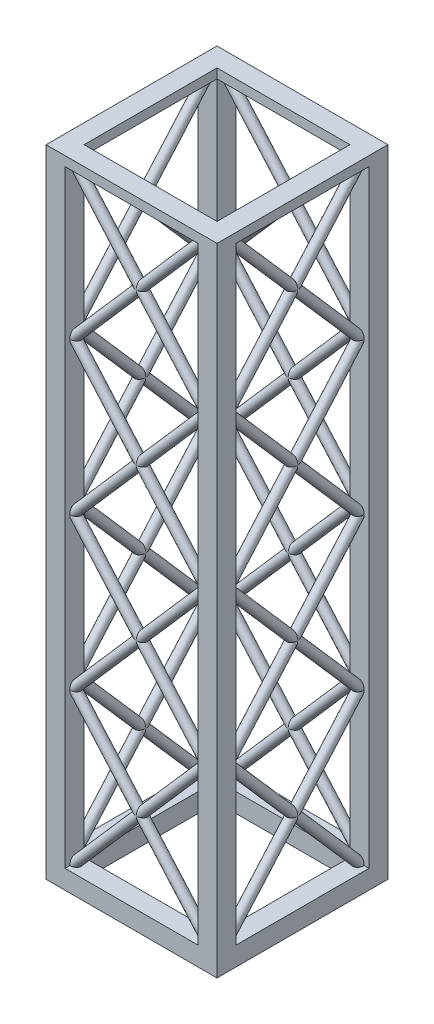
SolidWorks part; units mm, degrees
note: '?' marks a value the reader was unsure of.
ref_plane "Front Plane" through (0, 0, 0) normal (0, 0, 1) x (1, 0, 0)
ref_plane "Top Plane" through (0, 0, 0) normal (0, 1, 0) x (1, 0, 0)
ref_plane "Right Plane" through (0, 0, 0) normal (1, 0, 0) x (0, 0, -1)
sketch "Sketch1" plane through (0, 0, 0) normal (0, 1, 0) x (1, 0, 0)
  line L0 (-45, 45) -> (-45, -45)
  line L1 (-40, 40) -> (40, 40) construction
  line L2 (-40, 40) -> (-40, -40) construction
  line L3 (-40, -40) -> (40, -40) construction
  line L4 (40, 40) -> (40, -40) construction
  line L5 (-40, 40) -> (40, -40) construction
  line L6 (-40, -40) -> (40, 40) construction
  line L11 (-45, -45) -> (45, -45)
  line L12 (45, 45) -> (45, -45)
  line L13 (-45, 45) -> (45, 45)
  line L14 (-35, 35) -> (-35, -35)
  line L15 (-35, -35) -> (35, -35)
  line L16 (35, 35) -> (35, -35)
  line L17 (-35, 35) -> (35, 35)
  point P0 (0, 0)
  dimension "D1" = 80
  dimension "D2" = 80
  dimension "D3" = 5
  dimension "D4" = 5
ref_axis "Axis1" through (0, 367.5, 0) along (0, -1, 0)?
extrude "Boss-Extrude2" add sketch "Sketch1" along normal blind 10
sketch "Sketch2" plane through (0, 10, 0) normal (0, 1, 0) x (1, 0, 0)
  line L0 (-35, -35) -> (-45, -45) construction
  line L2 (-45, -45) -> (-35, -45)
  line L3 (-45, -45) -> (-45, -35)
  line L4 (-45, -35) -> (-35, -35)
  line L5 (-35, -45) -> (-35, -35)
  line L6 (-45, -45) -> (-35, -35) construction
  line L7 (-45, -35) -> (-35, -45) construction
  point P4 (-40, -40)
extrude "Boss-Extrude3" add sketch "Sketch2" along normal blind 320
pattern_circular "CirPattern2" count 4 over 360 about axis through (0, 0, 0) along (0, 1, 0) of "Boss-Extrude3"
sketch "Sketch3" plane through (0, 330, 0) normal (0, 1, 0) x (1, 0, 0)
  line L0 (-35, -35) -> (35, -35) construction
  line L1 (-45, -45) -> (45, -45)
  line L2 (-45, -45) -> (-45, 45)
  line L3 (-45, 45) -> (45, 45)
  line L4 (45, -45) -> (45, 45)
  line L5 (-45, -45) -> (45, 45) construction
  line L6 (-45, 45) -> (45, -45) construction
  line L7 (35, -35) -> (35, 35) construction
  line L8 (35, 35) -> (-35, 35) construction
  line L9 (-35, 35) -> (-35, -35) construction
  line L10 (-35, -35) -> (35, -35)
  line L11 (35, -35) -> (35, 35)
  line L12 (35, 35) -> (-35, 35)
  line L13 (-35, 35) -> (-35, -35)
  point P0 (0, 0)
extrude "Boss-Extrude4" add sketch "Sketch3" along normal blind 5
ref_plane "Plane1" through (0, 0, 40) normal (0, 0, -1) x (-1, 0, 0)
sketch "Sketch4" plane through (0, 0, 40) normal (0, 0, -1) x (-1, 0, 0)
  line L0 (-35, 10) -> (35, 90.0553)
  line L1 (35, 330) -> (35, 10) construction
  line L2 (35, 90.0553) -> (-35, 90.0553) construction
  line L3 (-35, 330) -> (-35, 10) construction
  point P9 (0, 0)
  point P10 (45.4056, 90.0553)
revolve "Revolve-Thin1" add sketch "Sketch4" angle 360 about L0 wall 2.5
mirror "Mirror1" about plane through (0, 0, 0) normal (1, 0, 0) of "Revolve-Thin1"
pattern_linear "LPattern1" count 4 spacing 80 along (0, 1, 0) of "Mirror1", "Revolve-Thin1"
pattern_circular "CirPattern3" count 4 over 360 about axis through (0, 0, 0) along (0, 1, 0) of "LPattern1", "Revolve-Thin1", "Mirror1"
